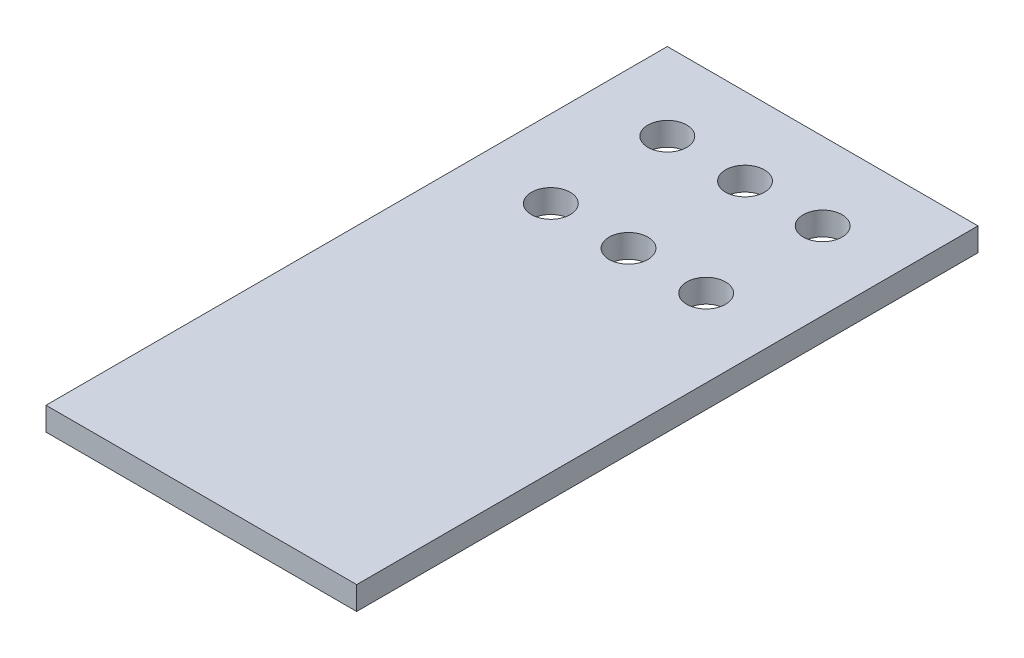
SolidWorks part; units mm, degrees
ref_plane "Front Plane" through (0, 0, 0) normal (0, 0, 1) x (1, 0, 0)
ref_plane "Top Plane" through (0, 0, 0) normal (0, 1, 0) x (1, 0, 0)
ref_plane "Right Plane" through (0, 0, 0) normal (1, 0, 0) x (0, 0, -1)
sketch "Sketch1" plane through (0, 0, 0) normal (0, 1, 0) x (1, 0, 0)
  line L1 (-25.4, -50.8) -> (25.4, -50.8)
  line L2 (-25.4, -50.8) -> (-25.4, 50.8)
  line L3 (-25.4, 50.8) -> (25.4, 50.8)
  line L4 (25.4, -50.8) -> (25.4, 50.8)
  line L5 (-25.4, -50.8) -> (25.4, 50.8) construction
  line L6 (-25.4, 50.8) -> (25.4, -50.8) construction
  point P0 (0, 0)
  dimension "D1" = 50.8
  dimension "D2" = 101.6
extrude "Boss-Extrude1" add sketch "Sketch1" along normal blind 3.81
sketch "Sketch2" plane through (0, 3.81, 0) normal (0, 1, 0) x (1, 0, 0)
  line L0 (-25.4, 50.8) -> (-25.4, -50.8) construction
  line L2 (-25.4, -50.8) -> (25.4, -50.8) construction
  circle A0 centre (-12.7, 19.05) radius 3.175
  dimension "D1" = 6.35
  dimension "D2" = 12.7
  dimension "D3" = 69.85
extrude "Cut-Extrude1" cut sketch "Sketch2" against normal blind 6.35
pattern_linear "LPattern1" count 2 spacing 19.05 along (0, 0, -1) count 3 spacing 12.7 along (1, 0, 0) of "Cut-Extrude1"
